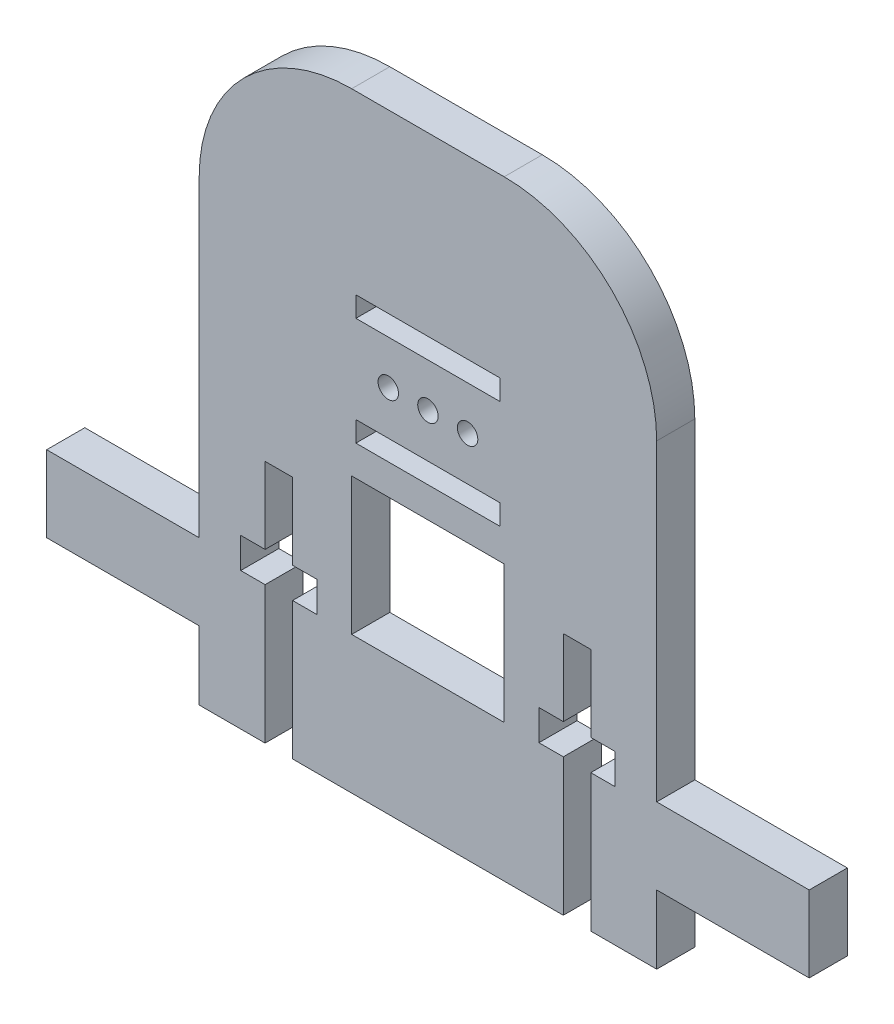
SolidWorks part; units mm, degrees
ref_plane "Front Plane" through (0, 0, 0) normal (0, 0, 1) x (1, 0, 0)
ref_plane "Top Plane" through (0, 0, 0) normal (0, 1, 0) x (1, 0, 0)
ref_plane "Right Plane" through (0, 0, 0) normal (1, 0, 0) x (0, 0, -1)
sketch "Sketch1" plane through (0, 0, 0) normal (0, 0, 1) x (1, 0, 0)
  line L0 (0, -1.7463) -> (0, 1.7463) construction
  line L1 (19.05, -25.4) -> (-19.05, -25.4)
  line L2 (19.05, -25.4) -> (19.05, -19.685)
  line L3 (19.05, 25.4) -> (-19.05, 25.4)
  line L4 (-19.05, -25.4) -> (-19.05, -19.685)
  line L5 (19.05, -25.4) -> (-19.05, 25.4) construction
  line L6 (19.05, 25.4) -> (-19.05, -25.4) construction
  line L7 (-19.05, -19.685) -> (-31.75, -19.685)
  line L9 (-19.05, -13.335) -> (-31.75, -13.335)
  line L10 (-31.75, -19.685) -> (-31.75, -13.335)
  line L11 (31.75, -19.685) -> (31.75, -13.335)
  line L12 (19.05, -13.335) -> (31.75, -13.335)
  line L14 (19.05, -19.685) -> (31.75, -19.685)
  line L15 (-19.05, -13.335) -> (-19.05, 25.4)
  line L16 (19.05, -13.335) -> (19.05, 25.4)
  point P0 (0, 0)
  dimension "D1" = 38.1
  dimension "D2" = 50.8
  dimension "D3" = 12.7
  dimension "D4" = 6.35
  dimension "D5" = 5.715
extrude "Boss-Extrude1" add sketch "Sketch1" along normal blind 3.175
fillet "Fillet1" radius 12.7 2 edges at (19.05, 25.4, 1.5875) (-19.05, 25.4, 1.5875)
sketch "Sketch2" plane through (0, 0, 0) normal (0, 0, 1) x (1, 0, 0)
  line L0 (-19.05, -25.4) -> (19.05, -25.4) construction
  line L1 (0, -1.7463) -> (0, 1.7463) construction
  line L2 (-6, 9.015) -> (6, 10.715) construction
  line L3 (-6, 1.715) -> (6, 1.715)
  line L4 (-6, 1.715) -> (-6, 0.015)
  line L5 (-6, 0.015) -> (6, 0.015)
  line L6 (6, 1.715) -> (6, 0.015)
  line L7 (-6, 1.715) -> (6, 0.015) construction
  line L8 (-6, 0.015) -> (6, 1.715) construction
  line L9 (-6, 10.715) -> (6, 10.715)
  line L10 (-6, 9.015) -> (6, 9.015)
  line L11 (6, 10.715) -> (6, 9.015)
  line L12 (-6, 10.715) -> (6, 9.015) construction
  line L13 (-6, 10.715) -> (-6, 9.015)
  circle A0 centre (0, 5.365) radius 0.85
  circle A1 centre (-3.302, 5.365) radius 0.85
  circle A2 centre (3.302, 5.365) radius 0.85
  point P11 (0, 0.865)
  point P16 (0, 9.865)
  dimension "D2" = 1.7
  dimension "D1" = 30.765
  dimension "D4" = 1.7
  dimension "D5" = 12
  dimension "D6" = 1.7
  dimension "D7" = 12
  dimension "D8" = 4.5
  dimension "D9" = 4.5
  dimension "D3" = 2
extrude "Cut-Extrude1" cut sketch "Sketch2" along normal through all
sketch "Sketch3" plane through (0, 0, 0) normal (0, 0, 1) x (1, 0, 0)
  line L0 (-6, 0.015) -> (6, 0.015) construction
  line L1 (-13.5598, -5.08) -> (-11.2738, -5.08)
  line L2 (-13.5598, -5.08) -> (-13.5598, -25.4)
  line L3 (-13.5598, -25.4) -> (-11.2738, -25.4)
  line L4 (-11.2738, -5.08) -> (-11.2738, -25.4)
  line L5 (-13.5598, -5.08) -> (-11.2738, -25.4) construction
  line L6 (-13.5598, -25.4) -> (-11.2738, -5.08) construction
  line L7 (-6.35, -2.525) -> (6.35, -2.525)
  line L8 (-19.05, -25.4) -> (19.05, -25.4) construction
  line L9 (-6.35, -2.525) -> (-6.35, -13.955)
  line L10 (-15.5918, -11.43) -> (-9.2418, -11.43)
  line L11 (-15.5918, -11.43) -> (-15.5918, -13.97)
  line L12 (-15.5918, -13.97) -> (-9.2418, -13.97)
  line L13 (-9.2418, -11.43) -> (-9.2418, -13.97)
  line L14 (-15.5918, -11.43) -> (-9.2418, -13.97) construction
  line L15 (-15.5918, -13.97) -> (-9.2418, -11.43) construction
  line L16 (-6.35, -13.955) -> (6.35, -13.955)
  line L17 (6.35, -2.525) -> (6.35, -13.955)
  line L18 (-6.35, -2.525) -> (6.35, -13.955) construction
  line L19 (-6.35, -13.955) -> (6.35, -2.525) construction
  line L20 (0, -1.7463) -> (0, 1.7463) construction
  line L21 (15.5918, -13.97) -> (9.2418, -11.43) construction
  line L22 (15.5918, -11.43) -> (9.2418, -13.97) construction
  line L23 (13.5598, -25.4) -> (11.2738, -5.08) construction
  line L24 (13.5598, -5.08) -> (11.2738, -25.4) construction
  line L25 (9.2418, -11.43) -> (9.2418, -13.97)
  line L26 (15.5918, -13.97) -> (9.2418, -13.97)
  line L27 (15.5918, -11.43) -> (15.5918, -13.97)
  line L28 (15.5918, -11.43) -> (9.2418, -11.43)
  line L29 (11.2738, -5.08) -> (11.2738, -25.4)
  line L30 (13.5598, -25.4) -> (11.2738, -25.4)
  line L31 (13.5598, -5.08) -> (13.5598, -25.4)
  line L32 (13.5598, -5.08) -> (11.2738, -5.08)
  point P0 (-12.4168, -15.24)
  point P8 (-12.4168, -12.7)
  point P18 (0, -8.24)
  point P33 (12.4168, -12.7)
  point P34 (12.4168, -15.24)
  dimension "D1" = 20.32
  dimension "D2" = 2.286
  dimension "D3" = 12.7
  dimension "D4" = 2.54
  dimension "D5" = 6.35
  dimension "D6" = 12.7
  dimension "D7" = 11.43
  dimension "D8" = 2.54
extrude "Cut-Extrude2" cut sketch "Sketch3" along normal through all contours L3 L4 L1 L2 | L13 L12 L11 L10 | L9 L7 L17 L16 | L29 L30 L31 L32 | L25 L26 L27 L28
equation "\"motor offset\"=6mm"
equation "\"thickness0.25\"=0.225in"
equation "\"thickness0.125\"=0.122in"
